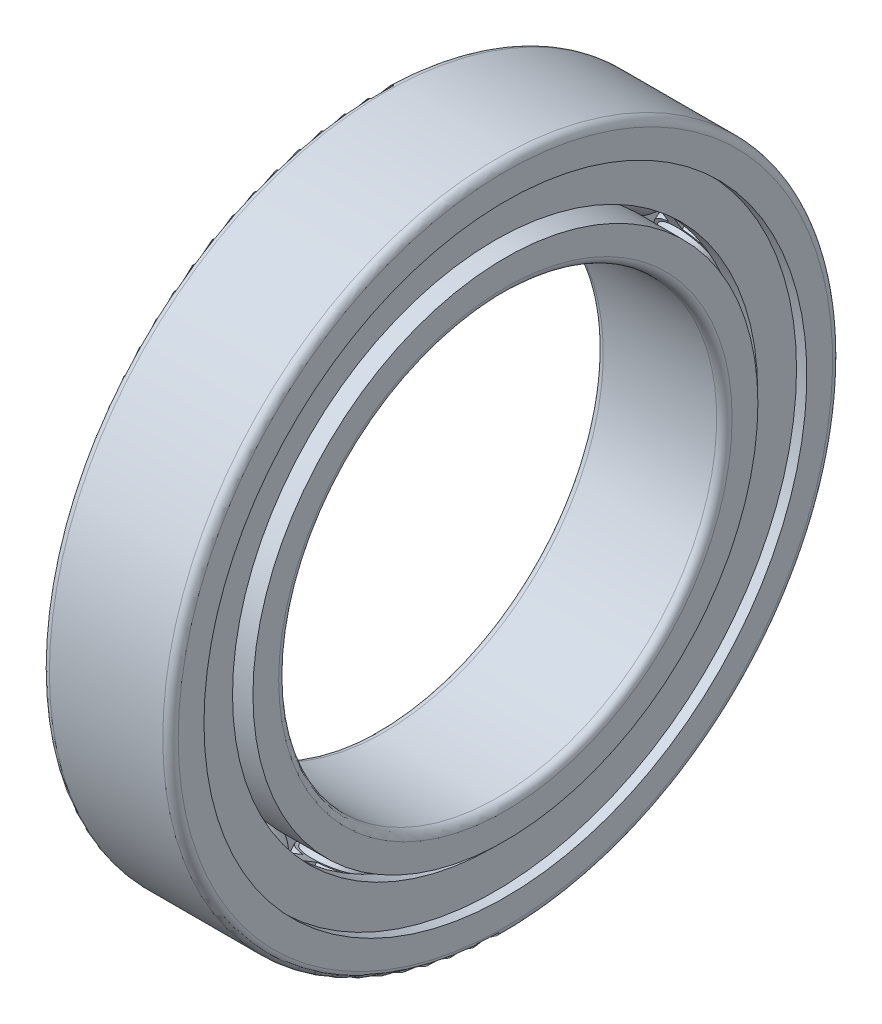
SolidWorks part; units mm, degrees
material "GCr4"
ref_plane "基准面1" through (0, 0, 0) normal (0, 0, 1) x (1, 0, 0)
ref_plane "基准面2" through (0, 0, 0) normal (0, 1, 0) x (1, 0, 0)
ref_plane "基准面3" through (0, 0, 0) normal (1, 0, 0) x (0, 0, -1)
sketch "尺寸草图" plane through (0, 0, 0) normal (0, 0, 1) x (1, 0, 0)
  point P0 (-67.8257, -75.4307)
  point P1 (-65.4447, -75.4307)
  point P2 (-71.0249, 50.7088)
  point P3 (-54.0249, 50.7088)
  point P4 (-45.0249, 50.7088)
  point P5 (-66.0249, 50.7088)
  point P6 (-71.0249, -10.9899)
  point P7 (-51.4249, -10.9899)
  point P8 (-46.7249, -10.9899)
  point P9 (-70.7249, -10.9899)
  point P10 (-51.8257, -75.4307)
  dimension "d" = 17
  dimension "DD" = 26
  dimension "B" = 5
  dimension "内圈外径DD2" = 19.6
  dimension "防尘圈径D3" = 24.3
  dimension "R" = 0.3
  dimension "球径DW" = 2.381
  dimension "球数Z" = 16
sketch "草图2" plane through (0, 0, 0) normal (0, 0, 1) x (1, 0, 0)
  line L0 (-12.4206, 0) -> (9.8128, 0) construction
  line L1 (0, 0) -> (0, 37.3563) construction
  line L2 (-5.5681, 10.75) -> (6.1049, 10.75) construction
  line L3 (-0.2619, 11.0774) -> (0.2619, 11.0774)
  line L4 (-0.2619, 11.0774) -> (-0.2619, 10.4226)
  line L5 (-0.2619, 10.4226) -> (0.2619, 10.4226)
  line L6 (0.2619, 11.0774) -> (0.2619, 10.4226)
  dimension "D1" = 0.5238
  dimension "D2" = 0.2619
  dimension "D3" = 0.6548
  dimension "D4" = 0.3274
  dimension "D5" = 10.75
revolve "基体-旋转" add sketch "草图2" angle 360 about L0
sketch "草图3" plane through (0, 0, 0) normal (0, 0, 1) x (1, 0, 0)
  line L0 (-5.5681, 10.75) -> (6.1049, 10.75) construction
  line L1 (-5.5681, 10.75) -> (6.1049, 10.75) construction
  line L2 (-12.4206, 0) -> (9.8128, 0) construction
  line L3 (-12.4206, 0) -> (9.8128, 0) construction
  line L4 (0, 0) -> (0, 37.3563) construction
  line L5 (0, 0) -> (0, 37.3563) construction
  line L6 (-1.3095, 10.75) -> (1.3095, 10.75)
  arc A0 (-1.3095, 10.75) -> (1.3095, 10.75) centre (0, 10.75) ccw
  dimension "Dwww" = 2.6191
  dimension "D2" = 1.3095
revolve "凸台-旋转1" add sketch "草图3" angle 360 about L1
pattern_circular "阵列(圆周)1" count 16 over 360 about axis through (-12.4206, 0, 0) along (1, 0, 0) of "凸台-旋转1"
sketch "草图4" plane through (0, 0, 0) normal (0, 0, 1) x (1, 0, 0)
  line L0 (0, 0) -> (8.1272, 0) construction
  line L1 (-12.4206, 0) -> (9.8128, 0) construction
  line L3 (-0.2619, 11.0774) -> (0.2619, 11.0774) construction
  line L4 (-1.3096, 12.3869) -> (1.3095, 12.3869)
  line L5 (-1.3096, 12.3869) -> (-1.3096, 11.0774)
  line L6 (-1.3096, 11.0774) -> (1.3095, 11.0774)
  line L7 (1.3095, 12.3869) -> (1.3095, 11.0774)
revolve "切除-旋转1" cut sketch "草图4" angle 360 about L0
sketch "草图5" plane through (0, 0, 0) normal (0, 0, 1) x (1, 0, 0)
  line L0 (0, 0) -> (8.2665, 0) construction
  line L1 (-12.4206, 0) -> (9.8128, 0) construction
  line L2 (-0.2619, 10.4226) -> (0.2619, 10.4226) construction
  line L3 (-1.3096, 10.4226) -> (1.3095, 10.4226)
  line L4 (-1.3096, 10.4226) -> (-1.3096, 9.1131)
  line L5 (-1.3096, 9.1131) -> (1.3095, 9.1131)
  line L6 (1.3095, 10.4226) -> (1.3095, 9.1131)
revolve "切除-旋转2" cut sketch "草图5" angle 360 about L0
sketch "草图6" plane through (0, 0, 0) normal (0, 0, 1) x (1, 0, 0)
  line L0 (0, 0) -> (5.5439, 0) construction
  line L1 (-12.4206, 0) -> (9.8128, 0) construction
  line L2 (0, 0) -> (0, 11.4011) construction
  line L3 (-5.5681, 10.75) -> (6.1049, 10.75) construction
  line L4 (-5.5681, 10.75) -> (6.1049, 10.75) construction
  line L5 (-1.1905, 10.75) -> (1.1905, 10.75)
  arc A0 (-1.1905, 10.75) -> (1.1905, 10.75) centre (0, 10.75) ccw
  dimension "Dw" = 2.381
revolve "凸台-旋转2" add sketch "草图6" angle 360 about L4
pattern_circular "阵列(圆周)2" count 16 over 360 about axis through (-12.4206, 0, 0) along (1, 0, 0) of "凸台-旋转2"
sketch "草图7" plane through (0, 0, 0) normal (0, 0, 1) x (1, 0, 0)
  line L0 (0, 0) -> (6.6488, 0) construction
  line L1 (0, 0) -> (0, 16.8954) construction
  line L2 (-2.2, 13) -> (2.2, 13)
  line L3 (-2.5, 12.7) -> (-2.5, 11.7)
  line L4 (-2.5, 11.7) -> (-2.1, 11.7)
  line L5 (2.5, 12.7) -> (2.5, 11.7)
  line L6 (0.7008, 11.7) -> (1.5648, 11.7)
  line L7 (2.1, 11.7) -> (2.5, 11.7)
  line L8 (1.5648, 12.15) -> (2.1, 12.15)
  line L9 (1.5648, 12.15) -> (1.5648, 11.7)
  line L10 (-1.5648, 11.7) -> (-0.7008, 11.7)
  line L11 (2.1, 12.15) -> (2.1, 11.7)
  line L12 (-2.1, 12.15) -> (-1.5648, 12.15)
  line L13 (-2.1, 12.15) -> (-2.1, 11.7)
  line L15 (-1.5648, 12.15) -> (-1.5648, 11.7)
  arc A0 (-2.2, 13) -> (-2.5, 12.7) centre (-2.2, 12.7) ccw
  arc A1 (2.2, 13) -> (2.5, 12.7) centre (2.2, 12.7) cw
  arc A2 (1.1446, 11.0774) -> (-1.1446, 11.0774) centre (0, 10.75) ccw construction
  arc A3 (0.7175, 11.7) -> (0, 9.5595) centre (0, 10.75) ccw construction
  arc A4 (0.7008, 11.7) -> (-0.7008, 11.7) centre (0, 10.75) ccw
  point P10 (-2.5, 13)
  point P13 (2.5, 13)
  dimension "R" = 0.3
  dimension "D1" = 0.01
  dimension "D2" = 23.4
  dimension "D" = 26
  dimension "D3" = 2.5
  dimension "B" = 5
  dimension "D4" = 0.5352
  dimension "D5" = 24.3
  dimension "D6" = 0.4
  dimension "D7" = 0.5352
  dimension "D8" = 0.4
revolve "凸台-旋转3" add sketch "草图7" angle 360 about L0
sketch "草图8" plane through (0, 0, 0) normal (0, 0, 1) x (1, 0, 0)
  line L0 (-12.4206, 0) -> (9.8128, 0) construction
  line L1 (-12.4206, 0) -> (9.8128, 0) construction
  line L2 (2.5, 12.7) -> (2.5, 11.7) construction
  line L3 (-2.5, 9.8) -> (-0.7008, 9.8)
  line L4 (-2.5, 9.8) -> (-2.5, 8.8)
  line L5 (-2.2, 8.5) -> (2.2, 8.5)
  line L6 (2.5, 9.8) -> (2.5, 8.8)
  line L7 (-2.5, 12.7) -> (-2.5, 11.7) construction
  line L8 (0.7008, 9.8) -> (2.5, 9.8)
  arc A0 (-2.5, 8.8) -> (-2.2, 8.5) centre (-2.2, 8.8) ccw
  arc A1 (2.2, 8.5) -> (2.5, 8.8) centre (2.2, 8.8) ccw
  arc A2 (-1.1446, 10.4226) -> (1.1446, 10.4226) centre (0, 10.75) ccw construction
  arc A3 (-1.1446, 10.4226) -> (1.1446, 10.4226) centre (0, 10.75) ccw construction
  arc A4 (-0.7008, 9.8) -> (0.7008, 9.8) centre (0, 10.75) ccw
  dimension "D1" = 0.3
  dimension "DD" = 17
  dimension "D2" = 0.01
  dimension "DD2" = 19.6
revolve "凸台-旋转4" add sketch "草图8" angle 360 about L1
sketch "草图10" plane through (0, 0, 0) normal (0, 0, 1) x (1, 0, 0)
  line L0 (1.5648, -11.7) -> (1.5648, 11.7) construction
  line L1 (2.1, 12.15) -> (1.5648, 12.15)
  line L2 (2.1, 12.15) -> (2.1, 10.1929)
  line L3 (2.1, 10.1929) -> (1.5648, 10.1929)
  line L4 (1.5648, 12.15) -> (1.5648, 10.1929)
  line L5 (0.7008, 9.8) -> (2.5, 9.8) construction
  line L6 (0, 0) -> (-5.3515, 0) construction
  line L7 (-12.4206, 0) -> (9.8128, 0) construction
  dimension "D1" = 0.3929
revolve "凸台-旋转5" add sketch "草图10" angle 360 about L6
mirror "镜向1" about plane through (0, 0, 0) normal (1, 0, 0) of "凸台-旋转5"
equation "\"Z@阵列(圆周)1\"=\"球数Z@尺寸草图\" "
equation "\"D5@草图7\" = \"防尘圈径D3@尺寸草图\""
equation "\"DD@草图8\"=\"d@尺寸草图\""
equation "\"D@草图7\"=\"DD@尺寸草图\""
equation "\"B@草图7\"=\"B@尺寸草图\" "
equation "\"DD2@草图8\"=\"内圈外径DD2@尺寸草图\""
equation "\"R@草图7\"=\"R@尺寸草图\""
equation "\"Dw@草图6\"=\"球径DW@尺寸草图\""
equation "\"Dwww@草图3\" = 1.1*\"Dw@草图6\""
equation "\"D3@草图2\" = 0.25*\"Dwww@草图3\""
equation "\"D4@草图2\" = \"D3@草图2\"/2"
equation "\"D2@草图3\" = 0.5*\"Dwww@草图3\""
equation "\"D1@草图2\" = 0.2*\"Dwww@草图3\""
equation "\"D2@草图2\" = 0.5*\"D1@草图2\""
equation "\"切除位置@草图4\" = \"Dwww@草图3\"/2"
equation "\"D1@阵列(圆周)2\" = \"Z@阵列(圆周)1\""
equation "\"D3@草图7\" = \"B@草图7\" / 2"
equation "\"D1@草图8\" = \"R@草图7\""
equation "\"D2@草图7\" = 0.9*\"D@草图7\""
equation "\"D5@草图2\" = 0.25* ( \"D2@草图7\" + \"DD2@草图8\" )  "
equation "\"D6@草图7\" = 0.08 * \"B@草图7\""
equation "\"D1@草图10\" = 0.15*\"Dwww@草图3\""
equation "\"D7@草图7\" = \"D4@草图7\" "
equation "\"D8@草图7\" = \"D6@草图7\""
